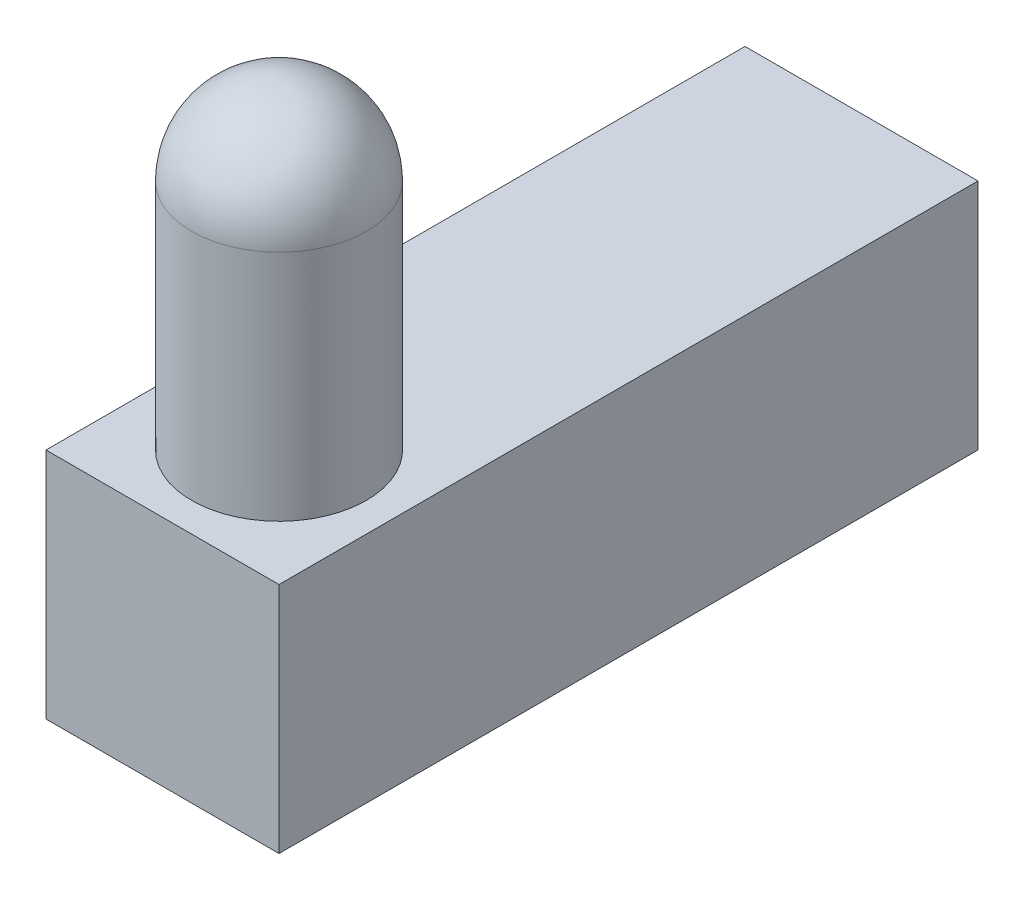
SolidWorks part; units mm, degrees
ref_plane "Front Plane" through (0, 0, 0) normal (0, 0, 1) x (1, 0, 0)
ref_plane "Top Plane" through (0, 0, 0) normal (0, 1, 0) x (1, 0, 0)
ref_plane "Right Plane" through (0, 0, 0) normal (1, 0, 0) x (0, 0, -1)
sketch "Sketch1" plane through (0, 0, 0) normal (0, 1, 0) x (1, 0, 0)
  line L1 (0, 0) -> (101.6, 0)
  line L2 (0, 0) -> (0, 304.8)
  line L3 (0, 304.8) -> (101.6, 304.8)
  line L4 (101.6, 0) -> (101.6, 304.8)
extrude "Boss-Extrude1" add sketch "Sketch1" along normal blind 101.6
sketch "Sketch2" plane through (0, 101.6, 0) normal (0, 1, 0) x (1, 0, 0)
  circle A0 centre (50.8, 50.8) radius 38.1
extrude "Boss-Extrude2" add sketch "Sketch2" along normal blind 101.6
sketch "Sketch5" plane through (0, 203.2, 0) normal (0, 1, 0) x (1, 0, 0)
  line L0 (88.7732, 53.9059) -> (12.8268, 47.6941)
  arc A0 (88.7732, 53.9059) -> (12.8268, 47.6941) centre (50.8, 50.8) ccw
revolve "Revolve3" add sketch "Sketch5" angle 360 about L0
